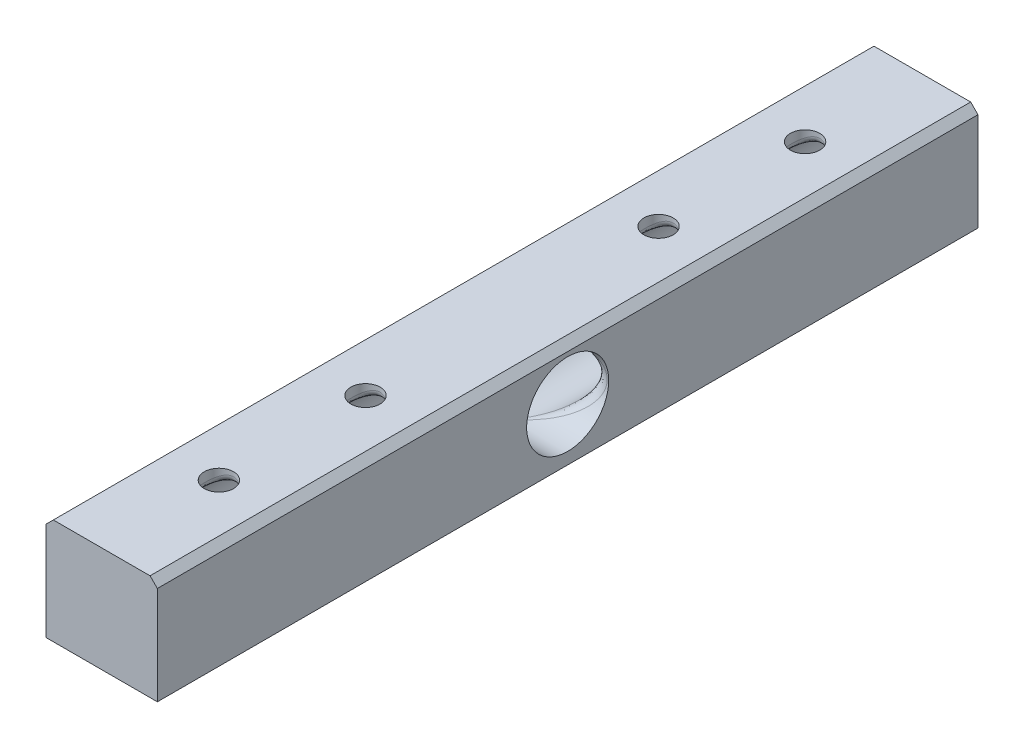
SolidWorks part; units mm, degrees
material "1060 Alaşım"
ref_plane "Ön Düzlem" through (0, 0, 0) normal (0, 0, 1) x (1, 0, 0)
ref_plane "Üst Düzlem" through (0, 0, 0) normal (0, 1, 0) x (1, 0, 0)
ref_plane "Sağ Düzlem" through (0, 0, 0) normal (1, 0, 0) x (0, 0, -1)
sketch "Çizim1" plane through (0, 0, 0) normal (0, 1, 0) x (1, 0, 0)
  line L1 (0, 0) -> (38, 0)
  line L2 (0, 0) -> (0, 280)
  line L3 (0, 280) -> (38, 280)
  line L4 (38, 0) -> (38, 280)
  dimension "D1" = 38
  dimension "D2" = 280
extrude "Yükseklik-Ekstrüzyon1" add sketch "Çizim1" along normal blind 36
chamfer "Pah1" distance 2.5 angle 45 2 edges at (0, 36, -140) (38, 36, -140)
sketch "Çizim2" plane through (0, 0, 0) normal (0, 0, 1) x (1, 0, 0)
  line L0 (0, 0) -> (38, 0) construction
  circle A0 centre (19, 18) radius 14
  point P5 (19, 0)
  dimension "D1" = 28
  dimension "D2" = 18
sketch "Çizim3" plane through (0, 36, 0) normal (0, 1, 0) x (1, 0, 0)
  line L0 (2.5, 0) -> (35.5, 0) construction
  line L1 (35.5, 280) -> (2.5, 280) construction
  circle A0 centre (19, 40) radius 5
  circle A1 centre (19, 90) radius 5
  circle A2 centre (19, 190) radius 5
  circle A3 centre (19, 240) radius 5
  point P4 (19, 0)
  point P5 (0, 0)
  point P12 (0, 0)
  dimension "D1" = 10
  dimension "D2" = 40
  dimension "D3" = 40
  dimension "D4" = 50
  dimension "D5" = 50
sketch "Çizim4" plane through (38, 0, 0) normal (1, 0, 0) x (0, 0, -1)
  line L0 (0, 0) -> (280, 0) construction
  line L2 (0, 36) -> (280, 36) construction
  circle A0 centre (140, 18) radius 14
  point P4 (140, 0)
  dimension "D1" = 28
  dimension "D2" = 18
extrude "Kes-Ekstrüzyon7" cut sketch "Çizim2" against normal blind 270 from offset 5 offset against normal yes
extrude "Kes-Ekstrüzyon8" cut sketch "Çizim3" against normal up to next
extrude "Kes-Ekstrüzyon9" cut sketch "Çizim4" against normal up to next
fillet "Radyus1" radius 2.5 4 edges at (19.8073, 31.9767, -44.9344) (19.8073, 31.9767, -94.9344) (19.8073, 31.9767, -244.9344) (19.8073, 31.9767, -194.9344)
fillet "Radyus2" radius 4.5 2 edges at (33, 18, -154) (33, 18, -126)
